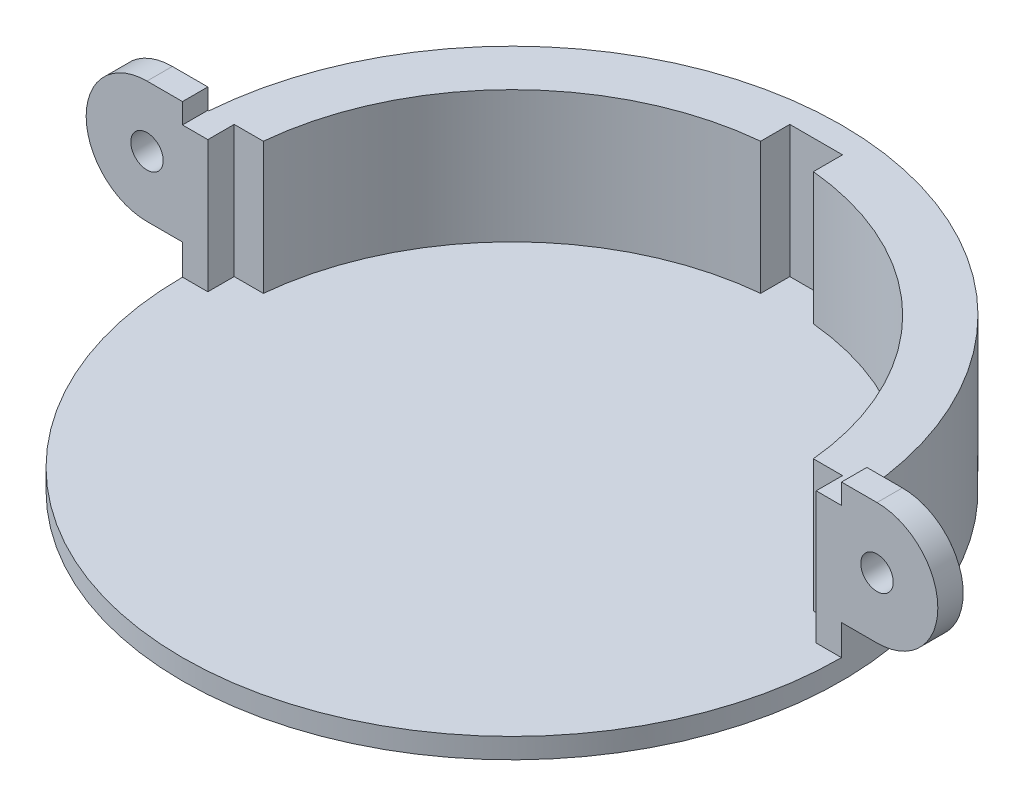
SolidWorks part; units mm, degrees
ref_plane "Front Plane" through (0, 0, 0) normal (0, 0, 1) x (1, 0, 0)
ref_plane "Top Plane" through (0, 0, 0) normal (0, 1, 0) x (1, 0, 0)
ref_plane "Right Plane" through (0, 0, 0) normal (1, 0, 0) x (0, 0, -1)
sketch "Sketch1" plane through (0, 0, 0) normal (0, 1, 0) x (1, 0, 0)
  circle A0 centre (0, 0) radius 32.5
  dimension "D1" = 65
extrude "Boss-Extrude1" add sketch "Sketch1" along normal blind 2
sketch "Sketch2" plane through (0, 2, 0) normal (0, 1, 0) x (1, 0, 0)
  line L0 (0, -55) -> (0, 55) construction
  line L1 (2.6, -30) -> (-2.6, -30)
  line L2 (2.6, -30) -> (2.6, -26.0456)
  line L3 (2.6, -26.0456) -> (-2.6, -26.0456)
  line L4 (-2.6, -30) -> (-2.6, -26.0456)
  line L5 (2.6, -30) -> (-2.6, -26.0456) construction
  line L6 (2.6, -26.0456) -> (-2.6, -30) construction
  line L7 (-30, -2.6) -> (-30, 2.6)
  line L8 (-30, -2.6) -> (-26.0456, -2.6)
  line L9 (-30, 2.6) -> (-26.0456, 2.6)
  line L10 (-26.0456, -2.6) -> (-26.0456, 2.6)
  line L11 (-2.6, 30) -> (2.6, 30)
  line L12 (-2.6, 30) -> (-2.6, 26.0456)
  line L13 (2.6, 30) -> (2.6, 26.0456)
  line L14 (-2.6, 26.0456) -> (2.6, 26.0456)
  line L15 (30, 2.6) -> (30, -2.6)
  line L16 (30, 2.6) -> (26.0456, 2.6)
  line L17 (30, -2.6) -> (26.0456, -2.6)
  line L18 (26.0456, 2.6) -> (26.0456, -2.6)
  circle A0 centre (0, 0) radius 27.1
  circle A1 centre (0, 0) radius 27.25
  circle A2 centre (0, 0) radius 32.5
  point P4 (0, -28.0228)
  circle M7 centre (0, 0) radius 32.5
  dimension "D1" = 54.5
  dimension "D2" = 54.2
  dimension "D3" = 30
  dimension "D4" = 5.2
  dimension "D5" = 4
extrude "Boss-Extrude2" add sketch "Sketch2" along normal blind 13 contours A0 L2 L1 L4 L8 L7 L9 L12 L11 L13 L16 L15 L17 M7 region at (-31.5808, 2, 0)
sketch "Sketch3" plane through (0, 0, 0) normal (0, -1, 0) x (1, 0, 0)
  circle A5 centre (0, 0) radius 5
  dimension "D1" = 10
extrude "Cut-Extrude2" [suppressed] cut sketch "Sketch3" against normal up to next contours A5
sketch "Sketch5" plane through (0, 0, 0) normal (0, -1, 0) x (1, 0, 0)
  line L1 (-9, -5.5) -> (9, -5.5) construction
  line L2 (-9, -5.5) -> (-9, 5.5) construction
  line L3 (-9, 5.5) -> (9, 5.5) construction
  line L4 (9, -5.5) -> (9, 5.5) construction
  line L5 (-9, -5.5) -> (9, 5.5) construction
  line L6 (-9, 5.5) -> (9, -5.5) construction
  circle A0 centre (9, 5.5) radius 1.3
  circle A1 centre (9, -5.5) radius 1.3
  circle A2 centre (-9, -5.5) radius 1.3
  circle A3 centre (-9, 5.5) radius 1.3
  point P0 (0, 0)
  dimension "D1" = 2.6
  dimension "D2" = 18
  dimension "D3" = 11
extrude "Cut-Extrude3" [suppressed] cut sketch "Sketch5" against normal up to next
sketch "Sketch6" plane through (0, 15, 0) normal (0, 1, 0) x (1, 0, 0)
  line L0 (-8.25, 0) -> (8.25, 0) construction
  line L1 (35.8547, 0) -> (-35.5353, 0)
  line L2 (35.8547, 0) -> (35.8547, -35.7749)
  line L3 (35.8547, -35.7749) -> (-35.5353, -35.7749)
  line L4 (-35.5353, 0) -> (-35.5353, -35.7749)
extrude "Cut-Extrude4" cut sketch "Sketch6" against normal up to surface (13 mm away) up to face at (0, 2, 0)
sketch "Sketch7" [suppressed] plane through (0, 0, 0) normal (1, 0, 0) x (0, 0, -1)
  line L0 (0, 8.25) -> (0, -8.25) construction
  line L1 (0, 2) -> (12, 2)
  line L2 (0, 2) -> (0, 5)
  line L3 (0, 5) -> (12, 5)
  line L4 (12, 2) -> (12, 5)
  line L5 (0, 2) -> (-32.5, 2) construction
  dimension "D1" = 3
  dimension "D2" = 12
sketch "Sketch8" plane through (0, 0, 0) normal (0, 0, 1) x (1, 0, 0)
  line L1 (36, 17) -> (32.5, 17)
  line L3 (36, 5) -> (30.5, 5)
  line L4 (30.5, 15) -> (30.5, 5)
  line L5 (32.5, 15) -> (32.5, 2) construction
  line L6 (32.5, 15) -> (-32.5, 15) construction
  line L7 (32.5, 15) -> (30.5, 15)
  line L8 (32.5, 15) -> (32.5, 17)
  arc A0 (36, 5) -> (36, 17) centre (36, 11) ccw
  circle A1 centre (36, 11) radius 1.6
  dimension "D5" = 3.2
  dimension "D1" = 2
  dimension "D2" = 3.5
  dimension "D3" = 12
  dimension "D4" = 4
extrude "Boss-Extrude3" add sketch "Sketch8" against normal blind 2.5
mirror "Mirror1" about plane through (0, 0, 0) normal (1, 0, 0) of "Boss-Extrude3"
